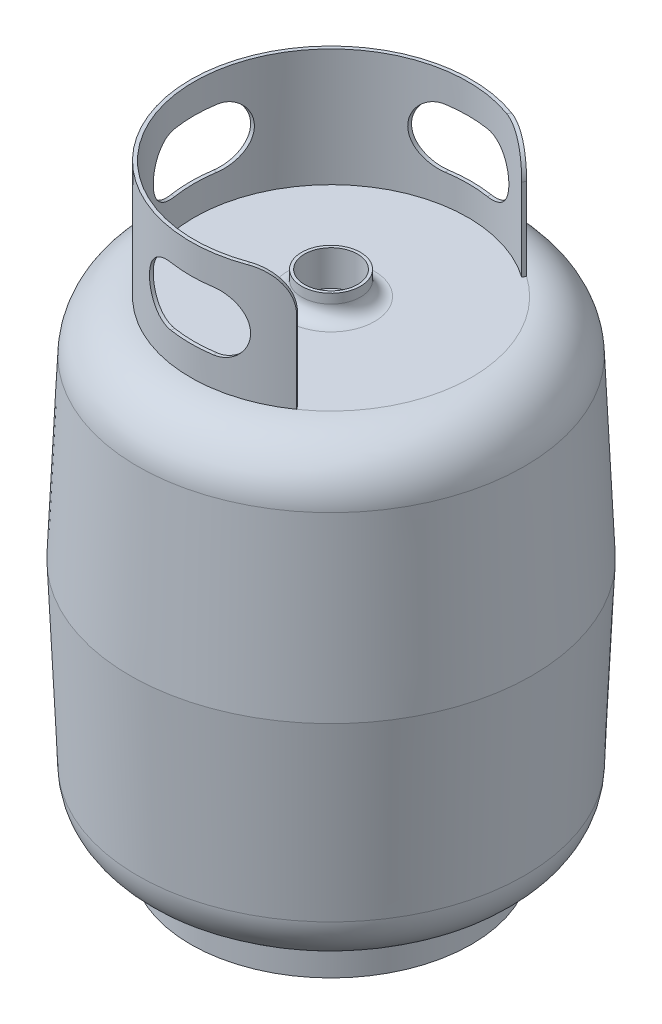
SolidWorks part; units mm, degrees
material "1060 Alloy"
ref_plane "Front Plane" through (0, 0, 0) normal (0, 0, 1) x (1, 0, 0)
ref_plane "Top Plane" through (0, 0, 0) normal (0, 1, 0) x (1, 0, 0)
ref_plane "Right Plane" through (0, 0, 0) normal (1, 0, 0) x (0, 0, -1)
sketch "Sketch1" plane through (0, 0, 0) normal (0, 0, 1) x (1, 0, 0)
  line L0 (0, -541.4696) -> (0, 541.4696) construction
  line L1 (0, 0) -> (119.4219, 0)
  line L2 (164.379, 43.0371) -> (170.9593, 193.75)
  line L3 (170.9593, 193.75) -> (164.379, 344.4629)
  line L4 (119.4219, 387.5) -> (37, 387.5)
  line L5 (25, 399.5) -> (25, 407.5)
  line L6 (25, 407.5) -> (0, 407.5)
  line L7 (0, 0) -> (0, 407.5) construction
  line L8 (0, 0) -> (0, 407.5)
  arc A0 (37, 387.5) -> (25, 399.5) centre (37, 399.5) cw
  arc A1 (119.4219, 0) -> (164.379, 43.0371) centre (119.4219, 45) ccw
  arc A2 (164.379, 344.4629) -> (119.4219, 387.5) centre (119.4219, 342.5) ccw
  point P4 (0, 0)
  point P11 (25, 387.5)
  point P14 (162.5, 0)
  point P18 (162.5, 387.5)
  dimension "D6" = 12
  dimension "D7" = 45
  dimension "D1" = 325
  dimension "D2" = 387.5
  dimension "D3" = 325
  dimension "D4" = 50
  dimension "D5" = 20
  dimension "D8" = 92.5
  dimension "92.5" = 92.5
revolve "Revolve2" add sketch "Sketch1" angle 360 about L7
sketch "Sketch2" plane through (0, 387.5, 0) normal (0, 1, 0) x (1, 0, 0)
  line L0 (0, 0) -> (68.4976, 97.8247)
  line L1 (0, 0) -> (68.4976, -97.8247)
  circle A0 centre (0, 0) radius 128.4219
  circle A1 centre (0, 0) radius 116.4219
  circle A2 centre (0, 0) radius 119.4219 construction
  circle M2 centre (0, 0) radius 119.4219
  dimension "D1" = 3
  dimension "D2" = 12
  dimension "D3" = 55
  dimension "D4" = 55
extrude "Boss-Extrude1" add sketch "Sketch2" along normal blind 100 contours A1 L0 L1 M2 region at (-116.7258, 387.5, 0)
sketch "Sketch4" plane through (0, 0, 0) normal (0, 0, 1) x (1, 0, 0)
  line L0 (0, 387.5) -> (0, 487.5) construction
  line L3 (68.4976, 387.5) -> (-119.4219, 387.5) construction
  line L4 (66.7768, 487.5) -> (-116.4219, 487.5) construction
  line L5 (18, 437.5) -> (-18, 437.5) construction
  line L6 (18, 412.5) -> (-18, 412.5)
  line L7 (18, 462.5) -> (-18, 462.5)
  arc A0 (18, 412.5) -> (18, 462.5) centre (18, 437.5) ccw
  arc A1 (-18, 462.5) -> (-18, 412.5) centre (-18, 437.5) ccw
  point P10 (0, 437.5)
  dimension "D1" = 50
  dimension "D2" = 36
extrude "Cut-Extrude1" cut sketch "Sketch4" against normal through all both and the other way through all
pattern_circular "CirPattern1" count 2 every 90 about axis through (0, 387.5, 0) along (0, -1, 0) of "Cut-Extrude1"
fillet "Fillet1" radius 30 1 edges at (67.6372, 487.5, 96.5959)
fillet "Fillet2" radius 30 1 edges at (67.6372, 487.5, -96.5959)
sketch "Sketch6" plane through (0, 0, 0) normal (0, -1, 0) x (1, 0, 0)
  circle A0 centre (0, 0) radius 131.4219
  circle A1 centre (0, 0) radius 116.4219
  circle A2 centre (0, 0) radius 119.4219 construction
  circle A3 centre (0, 0) radius 119.4219
  dimension "D1" = 12
  dimension "D2" = 3
  dimension "D3" = 12
extrude "Boss-Extrude2" add sketch "Sketch6" along normal blind 30 contours A3
sketch "Sketch7" plane through (0, -30, 0) normal (0, -1, 0) x (1, 0, 0)
  circle A0 centre (0, 0) radius 116.4219
  circle A1 centre (0, 0) radius 119.4219 construction
  dimension "D1" = 3
extrude "Cut-Extrude2" cut sketch "Sketch7" against normal blind 30 and the other way through all
sketch "Sketch8" plane through (0, 407.5, 0) normal (0, 1, 0) x (1, 0, 0)
  circle A0 centre (0, 0) radius 22.5
  dimension "D1" = 45
extrude "Cut-Extrude4" cut sketch "Sketch8" against normal blind 30
equation "\"A\"= 325"
equation "\"B\"= 387.5"
